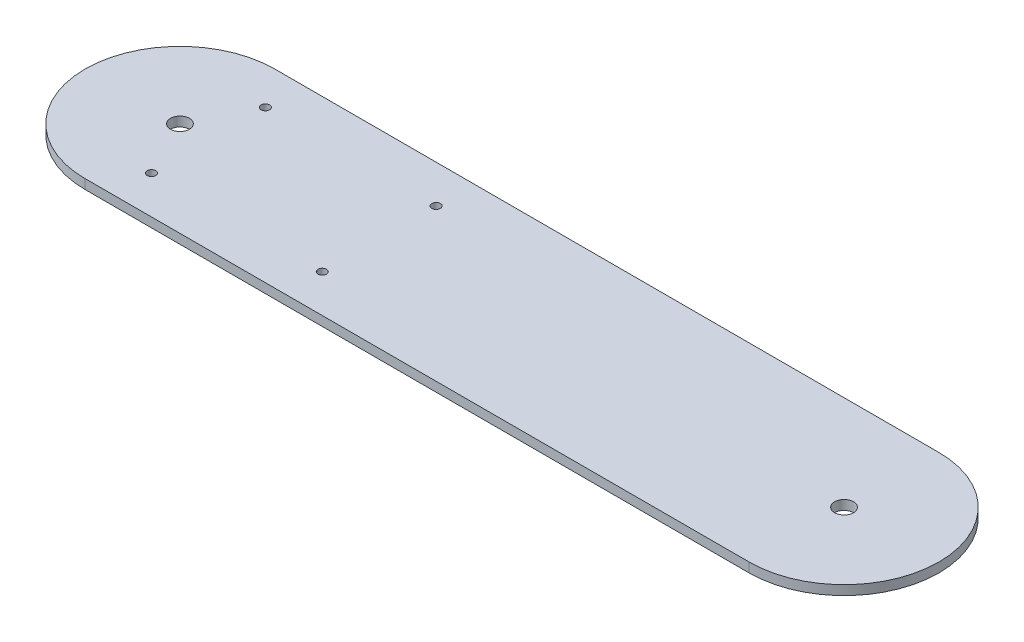
SolidWorks part; units mm, degrees
ref_plane "Front Plane" through (0, 0, 0) normal (0, 0, 1) x (1, 0, 0)
ref_plane "Top Plane" through (0, 0, 0) normal (0, 1, 0) x (1, 0, 0)
ref_plane "Right Plane" through (0, 0, 0) normal (1, 0, 0) x (0, 0, -1)
sketch "Sketch1" plane through (0, 0, 0) normal (0, 1, 0) x (1, 0, 0)
  line L0 (0, 0) -> (350, 0) construction
  line L1 (0, 50) -> (350, 50)
  line L2 (0, -50) -> (350, -50)
  circle A0 centre (0, 0) radius 5
  arc A1 (0, 50) -> (0, -50) centre (0, 0) ccw
  arc A2 (350, -50) -> (350, 50) centre (350, 0) ccw
  circle A3 centre (350, 0) radius 5
  dimension "D1" = 10
  dimension "D2" = 100
  dimension "D4" = 100
  dimension "D5" = 10
  dimension "D3" = 350
extrude "Boss-Extrude1" add sketch "Sketch1" along normal blind 5
sketch "Sketch2" plane through (0, 5, 0) normal (0, 1, 0) x (1, 0, 0)
  line L0 (15, 0) -> (0, 0) construction
  line L1 (15, 30) -> (105, 30) construction
  line L2 (15, 30) -> (15, -30) construction
  line L3 (15, -30) -> (105, -30) construction
  line L4 (105, 30) -> (105, -30) construction
  line L5 (15, 30) -> (105, -30) construction
  line L11 (25, -35) -> (95, 35) construction
  line L12 (25, 35) -> (95, -35) construction
  circle A2 centre (15, -30) radius 2.25
  circle A3 centre (105, -30) radius 2.25
  circle A4 centre (105, 30) radius 2.25
  circle A5 centre (15, 30) radius 2.25
  point P1 (60, 0)
  dimension "D4" = 2
  dimension "D6" = 70
  dimension "D1" = 60
  dimension "D2" = 90
  dimension "D3" = 15
  dimension "D7" = 70
  dimension "D5" = 2
extrude "Cut-Extrude1" cut sketch "Sketch2" against normal blind 5
sketch "Sketch3" [suppressed] plane through (0, 5, 0) normal (0, 1, 0) x (1, 0, 0)
  line L0 (15, 30) -> (105, -30) construction
  line L2 (25, -35) -> (95, -35)
  line L3 (25, -35) -> (25, 35)
  line L4 (25, 35) -> (95, 35)
  line L5 (95, -35) -> (95, 35)
  line L6 (25, -35) -> (95, 35) construction
  line L7 (25, 35) -> (95, -35) construction
  point P4 (60, 0)
  dimension "D1" = 70
  dimension "D2" = 70
extrude "Cut-Extrude2" [suppressed] cut sketch "Sketch3" against normal blind 20
sketch "Sketch4" [suppressed] plane through (0, 5, 0) normal (0, 1, 0) x (1, 0, 0)
  line L0 (15, 30) -> (105, -30) construction
  line L1 (60, 0) -> (350, 0) construction
  circle A0 centre (205, 0) radius 5
  dimension "D1" = 10
extrude "Cut-Extrude3" [suppressed] cut sketch "Sketch4" against normal blind 25
